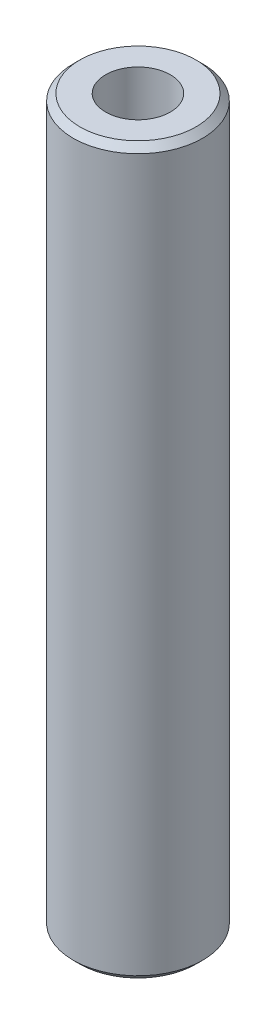
SolidWorks part; units mm, degrees
ref_plane "Front Plane" through (0, 0, 0) normal (0, 0, 1) x (1, 0, 0)
ref_plane "Top Plane" through (0, 0, 0) normal (0, 1, 0) x (1, 0, 0)
ref_plane "Right Plane" through (0, 0, 0) normal (1, 0, 0) x (0, 0, -1)
sketch "Sketch1" plane through (0, 0, 0) normal (0, 1, 0) x (1, 0, 0)
  circle A0 centre (0, 0) radius 25
  dimension "SHAFT_OD" = 50
extrude "Boss-Extrude1" add sketch "Sketch1" along normal blind 280.4503
sketch "Sketch2" plane through (0, 0, 0) normal (0, 1, 0) x (1, 0, 0)
  circle A0 centre (0, 0) radius 12.5253
  dimension "BORE_D" = 25.0507
extrude "Cut-Extrude1" cut sketch "Sketch2" along normal through all
chamfer "Chamfer1" distance 2.5458 angle 45 2 edges at (0, 280.4503, 25) (0, 0, 25)
